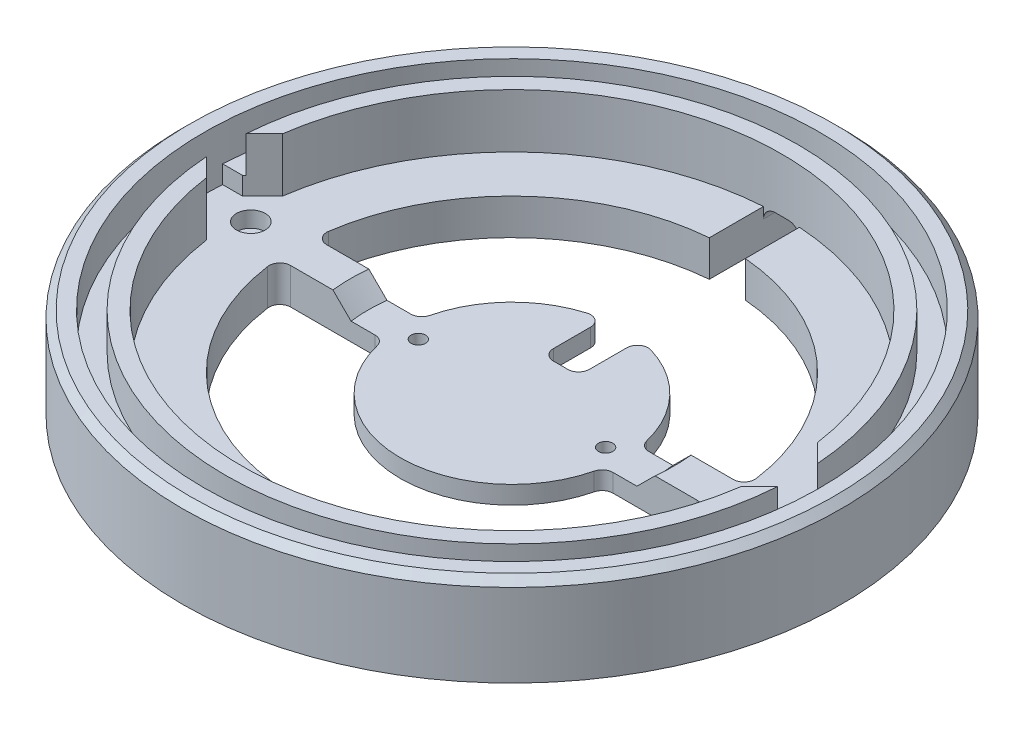
SolidWorks part; units mm, degrees
material "PBT General Purpose"
ref_plane "Front Plane" through (0, 0, 0) normal (0, 0, 1) x (1, 0, 0)
ref_plane "Top Plane" through (0, 0, 0) normal (0, 1, 0) x (1, 0, 0)
ref_plane "Right Plane" through (0, 0, 0) normal (1, 0, 0) x (0, 0, -1)
sketch "Sketch1" plane through (0, 0, 0) normal (0, 1, 0) x (1, 0, 0)
  circle A0 centre (0, 0) radius 91.5
  dimension "D1" = 183
extrude "Boss-Extrude1" add sketch "Sketch1" along normal blind 10
sketch "Sketch2" plane through (0, 10, 0) normal (0, 1, 0) x (1, 0, 0)
  line L1 (-60, 5) -> (60, 5)
  line L2 (-60, 5) -> (-60, -5)
  line L3 (-60, -5) -> (60, -5)
  line L4 (60, 5) -> (60, -5)
  line L5 (-60, 5) -> (60, -5) construction
  line L6 (-60, -5) -> (60, 5) construction
  circle A0 centre (0, 0) radius 60
  circle A1 centre (0, 0) radius 31
  dimension "D1" = 120
  dimension "D2" = 62
  dimension "D3" = 10
extrude "Cut-Extrude1" cut sketch "Sketch2" against normal through all contours A1 L1 A0 | A1 L3 A0 region at (0, 10, -32.0161) region at (0, 10, 32.0161)
sketch "Sketch3" plane through (0, 10, 0) normal (0, 1, 0) x (1, 0, 0)
  circle A0 centre (0, 0) radius 40
  dimension "D1" = 80
extrude "Cut-Extrude2" cut sketch "Sketch3" against normal blind 5
sketch "Sketch4" plane through (0, 10, 0) normal (0, 1, 0) x (1, 0, 0)
  circle A0 centre (0, 0) radius 75
  circle A1 centre (0, 0) radius 91.5
  dimension "D1" = 183
  dimension "D2" = 150
extrude "Boss-Extrude2" add sketch "Sketch4" along normal blind 5
sketch "Sketch5" plane through (0, 15, 0) normal (0, 1, 0) x (1, 0, 0)
  circle A0 centre (0, 0) radius 85.5
  circle A2 centre (0, 0) radius 91.5
  circle A3 centre (0, 0) radius 91.5
  dimension "D2" = 171
  dimension "D1" = 0
extrude "Boss-Extrude3" add sketch "Sketch5" along normal blind 10
chamfer "Chamfer1" distance 2 angle 45 1 edges at (0, 25, 91.5)
hole_wizard "Ø4.5 (4.5) Diameter Hole1" positions "Sketch8" profile "Sketch7" hole size "Ø4.5" standard "ISO" end condition through all
sketch "Sketch8" plane through (0, 10, 0) normal (0, 1, 0) x (1, 0, 0)
  line L0 (72.5, 0) -> (-72.5, 0) construction
  point P0 (-72.5, 0)
  point P2 (72.5, 0)
  dimension "D1" = 145
sketch "Sketch7" plane through (-72.5, 10, 0) normal (1, 0, 0) x (0, 0, 1)
  line L0 (0, 0) -> (0, 10)
  line L1 (0, 10) -> (2.25, 10)
  line L2 (2.25, 10) -> (2.25, 0)
  line L5 (2.25, 0) -> (0, 0)
  line L11 (0, -6.35) -> (0, 107.95) construction
  dimension "Thru Hole Dia." = 4.5
  dimension "Thru Hole Depth" = 10
sketch "Sketch9" plane through (0, 10, 0) normal (0, 1, 0) x (1, 0, 0)
  line L0 (-85.3537, 5) -> (85.3537, 5)
  line L2 (39.6863, 5) -> (30.5941, 5) construction
  line L3 (-85.3537, -5) -> (85.3537, -5)
  line L4 (-59.7913, -5) -> (-39.6863, -5) construction
  circle A0 centre (0, 0) radius 85.5 construction
  arc A1 (85.3537, -5) -> (85.3537, 5) centre (0, 0) ccw
  arc A2 (-85.3537, 5) -> (-85.3537, -5) centre (0, 0) ccw
extrude "Cut-Extrude3" cut sketch "Sketch9" along normal blind 91
fillet "Fillet1" radius 3 4 edges at (59.7913, 5, 5) (59.7913, 5, -5) (-59.7913, 5, -5) (-59.7913, 5, 5)
chamfer "Chamfer2" distance 5 angle 45 2 edges at (40, 10, 0) (-40, 10, 0)
chamfer "Chamfer3" distance 5 angle 45 4 edges at (74.8331, 12.5, 5) (74.8331, 12.5, -5) (-74.8331, 12.5, -5) (-74.8331, 12.5, 5) first distance on face at (80.0934, 12.5, 5) first distance on face at (80.0934, 12.5, -5) first distance on face at (-80.0934, 12.5, -5) first distance on face at (-80.0934, 12.5, 5)
ref_plane "Plane1" through (0, 0, -40) normal (0, 0, 1) x (1, 0, 0)
sketch "Sketch10" plane through (0, 0, -40) normal (0, 0, 1) x (1, 0, 0)
  line L0 (-91.5, 0) -> (91.5, 0) construction
  line L1 (-5, 10) -> (5, 10)
  line L2 (-5, 10) -> (-5, -10)
  line L3 (-5, -10) -> (5, -10)
  line L4 (5, 10) -> (5, -10)
  line L5 (-5, 10) -> (5, -10) construction
  line L6 (-5, -10) -> (5, 10) construction
  point P0 (0, 0)
  dimension "D1" = 10
  dimension "D2" = 10
extrude "Cut-Extrude4" cut sketch "Sketch10" against normal blind 91
fillet "Fillet2" radius 3 2 edges at (-5, 10, -83.0982) (5, 10, -83.0982)
fillet "Fillet3" radius 3 4 edges at (30.5941, 2.5, 5) (-30.5941, 2.5, 5) (-30.5941, 2.5, -5) (30.5941, 2.5, -5)
sketch "Sketch11" plane through (0, 15, 0) normal (0, 1, 0) x (1, 0, 0)
  line L0 (-74.2495, 10.5837) -> (-79.3078, 5.5254)
  line L1 (-74.2495, -10.5837) -> (-79.3078, -5.5254)
  line L2 (74.2495, 10.5837) -> (79.3078, 5.5254)
  line L3 (74.2495, -10.5837) -> (79.3078, -5.5254)
  line L4 (74.2495, -10.5837) -> (79.8331, -5) construction
  line L5 (-79.8331, 5) -> (-74.2495, 10.5837) construction
  line L6 (-79.8331, -5) -> (-74.2495, -10.5837) construction
  line L7 (74.2495, 10.5837) -> (79.8331, 5) construction
  arc A0 (74.2495, 10.5837) -> (-74.2495, 10.5837) centre (0, 0) ccw construction
  arc A1 (74.2495, 10.5837) -> (-74.2495, 10.5837) centre (0, 0) ccw
  arc A2 (-74.2495, -10.5837) -> (74.2495, -10.5837) centre (0, 0) ccw construction
  arc A3 (-74.2495, -10.5837) -> (74.2495, -10.5837) centre (0, 0) ccw
  arc A4 (79.3078, 5.5254) -> (-79.3078, 5.5254) centre (0, 0) ccw
  arc A5 (-79.3078, -5.5254) -> (79.3078, -5.5254) centre (0, 0) ccw
  dimension "D1" = 159
extrude "Boss-Extrude4" add sketch "Sketch11" along normal blind 10
sketch "Sketch12" plane through (0, 5, 0) normal (0, 1, 0) x (1, 0, 0)
  line L0 (-5, 74.8331) -> (-5, 59.7913) construction
  line L1 (-5, 48.5) -> (5, 48.5)
  line L2 (-5, 48.5) -> (-5, 13.5)
  line L3 (-5, 13.5) -> (5, 13.5)
  line L4 (5, 48.5) -> (5, 13.5)
  line L5 (-5, 48.5) -> (5, 13.5) construction
  line L6 (-5, 13.5) -> (5, 48.5) construction
  arc A0 (30.1297, 7.2941) -> (-30.1297, 7.2941) centre (0, 0) ccw construction
  point P0 (0, 31)
  dimension "D1" = 35
extrude "Cut-Extrude5" cut sketch "Sketch12" against normal blind 10
fillet "Fillet4" radius 3 4 edges at (5, 2.5, -30.5941) (-5, 2.5, -30.5941) (5, 2.5, -13.5) (-5, 2.5, -13.5)
sketch "Sketch13" plane through (0, 0, 0) normal (0, -1, 0) x (-1, 0, 0)
  line L0 (-26, 0) -> (26, 0) construction
  circle A0 centre (26, 0) radius 2
  circle A1 centre (-26, 0) radius 2
  dimension "D1" = 4
  dimension "D2" = 52
extrude "Cut-Extrude6" cut sketch "Sketch13" against normal blind 10
hole_wizard "CBORE for M4 Hex Socket Head Cap Screw1" positions "Sketch15" profile "Sketch14" counterbore size "M4" standard "ISO" end condition through all
sketch "Sketch15" plane through (0, 10, 0) normal (0, 1, 0) x (1, 0, 0)
  point P0 (-72.5, 0)
  point P2 (72.5, 0)
sketch "Sketch14" plane through (-72.5, 10, 0) normal (1, 0, 0) x (0, 0, 1)
  line L0 (0, 0) -> (0, 10)
  line L1 (0, 10) -> (2.25, 10)
  line L3 (2.25, 10) -> (2.25, 4.4)
  line L4 (2.25, 4.4) -> (4, 4.4)
  line L5 (4, 4.4) -> (4, 0)
  line L7 (4, 0) -> (0, 0)
  line L11 (0, -6.35) -> (0, 107.95) construction
  dimension "Thru Hole Dia." = 4.5
  dimension "Thru Hole Depth" = 10
  dimension "C'Bore Dia." = 8
  dimension "C'Bore Depth" = 4.4
